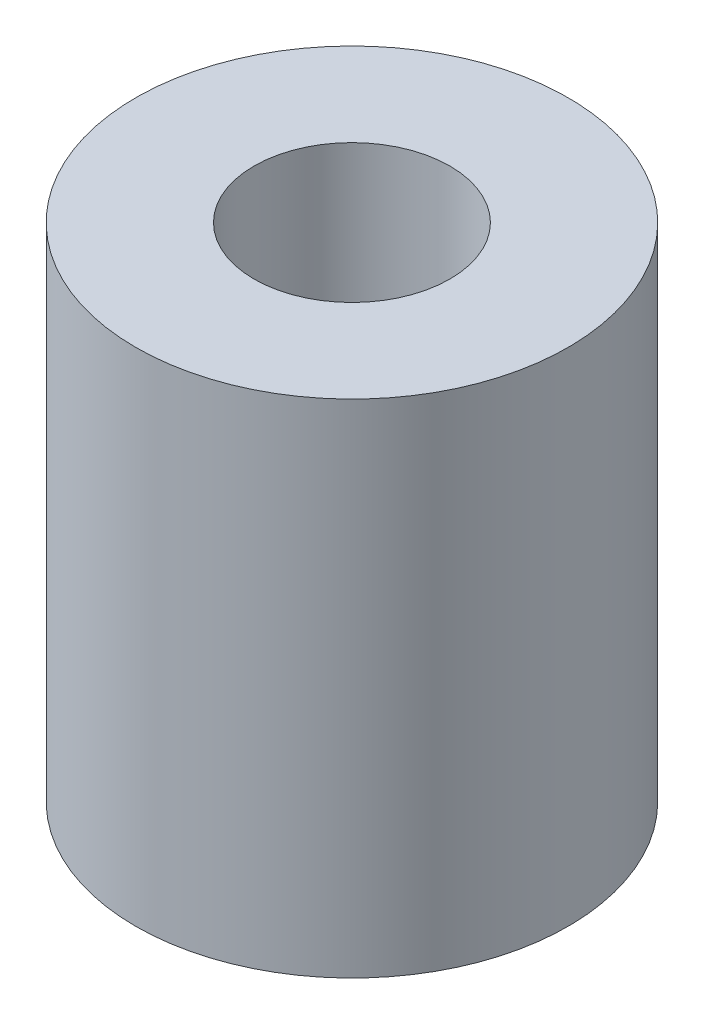
SolidWorks part; units mm, degrees
ref_plane "Front Plane" through (0, 0, 0) normal (0, 0, 1) x (1, 0, 0)
ref_plane "Top Plane" through (0, 0, 0) normal (0, 1, 0) x (1, 0, 0)
ref_plane "Right Plane" through (0, 0, 0) normal (1, 0, 0) x (0, 0, -1)
sketch "Sketch1" plane through (0, 0, 0) normal (0, 1, 0) x (1, 0, 0)
  circle A0 centre (0, 0) radius 6.9
  dimension "D1" = 13.8
extrude "Boss-Extrude1" add sketch "Sketch1" along normal blind 16
sketch "Sketch2" plane through (0, 16, 0) normal (0, 1, 0) x (1, 0, 0)
  circle A0 centre (0, 0) radius 3.125
  dimension "D1" = 6.25
extrude "Cut-Extrude1" cut sketch "Sketch2" against normal offset from surface (14 mm away) 2 up to face at (0, 0, 6.9)
